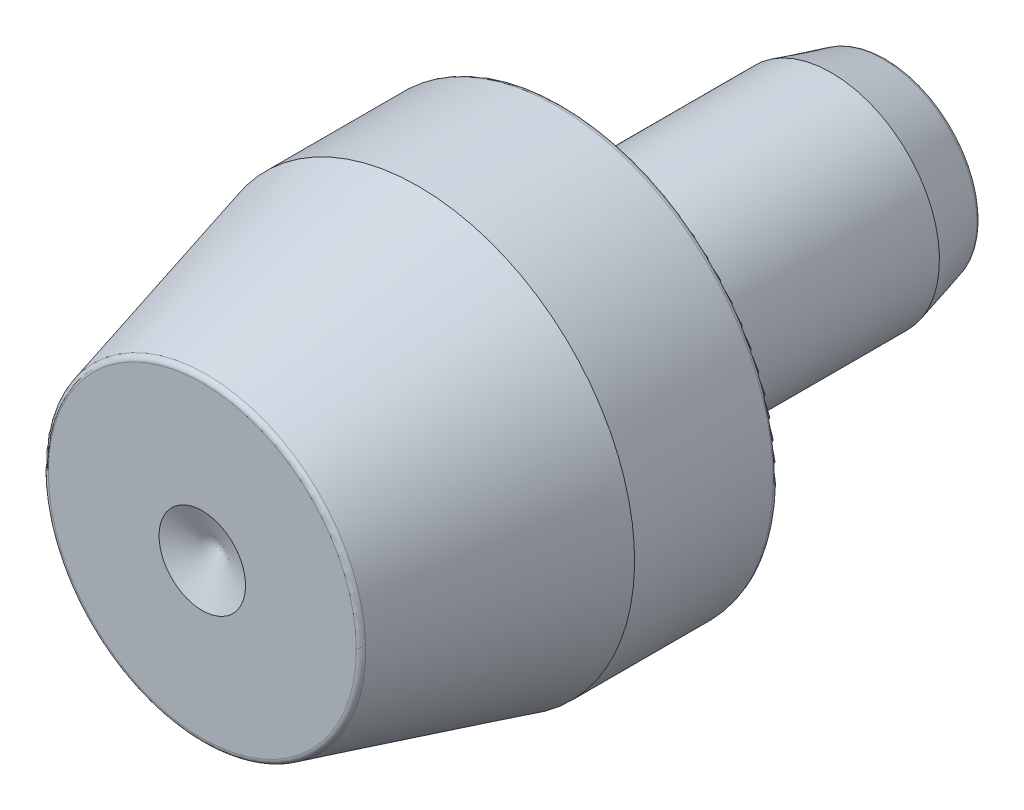
SolidWorks part; units mm, degrees
ref_plane "Front Plane" through (0, 0, 0) normal (0, 0, 1) x (1, 0, 0)
ref_plane "Top Plane" through (0, 0, 0) normal (0, 1, 0) x (1, 0, 0)
ref_plane "Right Plane" through (0, 0, 0) normal (1, 0, 0) x (0, 0, -1)
sketch "Sketch1" plane through (0, 0, 0) normal (1, 0, 0) x (0, 0, -1)
  line L0 (-9.5, 0) -> (9.5, 0) construction
  line L1 (-9.5, 1.2) -> (-9.5, 4.2743)
  line L2 (-9.386, 4.4228) -> (-3.5, 6)
  line L3 (-3.5, 6) -> (0.3463, 6)
  line L4 (0.5, 5.8462) -> (0.5, 3.4612)
  line L5 (1.4225, 3) -> (7.9625, 3)
  line L6 (7.9625, 3) -> (9.386, 2.6186)
  line L7 (9.5, 2.4701) -> (9.5, 0)
  line L8 (9.5, 0) -> (-9.0029, 0)
  line L9 (-9.5, 1.2) -> (-9.0029, 0)
  line L10 (-9.5, 1.2) -> (-9.5, 0) construction
  line L12 (0.3463, 3.3075) -> (0.3463, 3)
  line L13 (0.5, 2.8463) -> (1.2688, 2.8463)
  line L14 (1.2688, 2.8463) -> (1.4225, 3)
  arc A0 (0.5, 3.4612) -> (0.3463, 3.3075) centre (0.5, 3.3075) ccw
  arc A1 (0.3463, 3) -> (0.5, 2.8463) centre (0.5, 3) ccw
  arc A2 (0.5, 5.8462) -> (0.3463, 6) centre (0.3463, 5.8462) ccw
  arc A3 (-9.5, 4.2743) -> (-9.386, 4.4228) centre (-9.3463, 4.2743) cw
  arc A4 (9.5, 2.4701) -> (9.386, 2.6186) centre (9.3463, 2.4701) ccw
  point P20 (-9.5, 4.3923)
  point P25 (9.5, 2.588)
  dimension "D5" = 15
  dimension "D6" = 15
  dimension "D1" = 22.5
  dimension "D2" = 1.2
  dimension "D3" = 45
  dimension "D7" = 0.1538
  dimension "D8" = 0.1537
  dimension "D9" = 0.4612
  dimension "D10" = 0.7688
revolve "Revolve1" add sketch "Sketch1" angle 360 about L8
ref_plane "Contact Plane 1" through (0, 0, 9.5) normal (0, 0, 1) x (1, 0, 0)
ref_axis "Center Axis 1" through (0, 0, -7.15) along (0, 0, 1)
equation "\"D4@Sketch1\"=\"C@Sketch1\"*.25625"
equation "\"D2@Sketch1\"=\"A@Sketch1\"*.1"
equation "\"D7@Sketch1\"=\"D4@Sketch1\"*.1"
equation "\"D8@Sketch1\"=\"D7@Sketch1\""
equation "\"D9@Sketch1\"=\"D7@Sketch1\"*3"
equation "\"D10@Sketch1\"=\"D4@Sketch1\"*.5"
